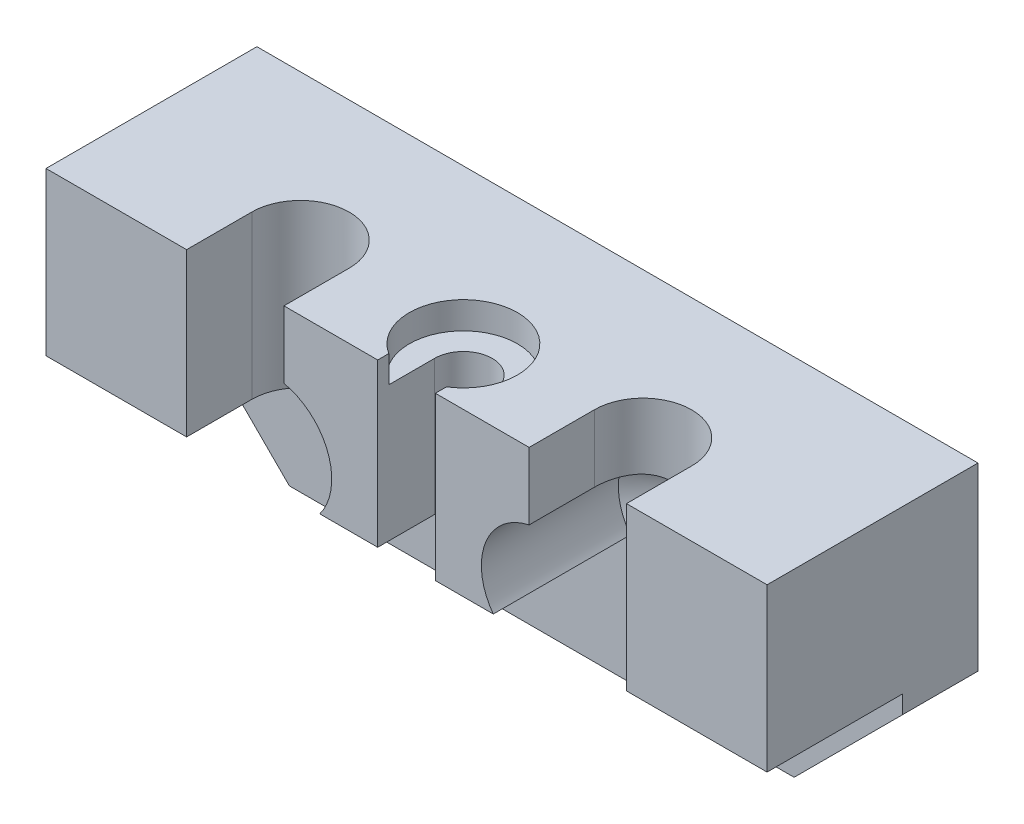
SolidWorks part; units mm, degrees
ref_plane "Front Plane" through (0, 0, 0) normal (0, 0, 1) x (1, 0, 0)
ref_plane "Top Plane" through (0, 0, 0) normal (0, 1, 0) x (1, 0, 0)
ref_plane "Right Plane" through (0, 0, 0) normal (1, 0, 0) x (0, 0, -1)
sketch "Sketch1" plane through (0, 0, 0) normal (0, 0, 1) x (1, 0, 0)
  line L1 (-20, 0) -> (20, 0)
  line L2 (-20, 0) -> (-20, 16)
  line L3 (-20, 16) -> (20, 16)
  line L4 (20, 0) -> (20, 16)
  dimension "D2" = 40
  dimension "D3" = 16
extrude "Boss-Extrude1" add sketch "Sketch1" along normal blind 12
sketch "Sketch2" plane through (0, 0, 12) normal (0, 0, 1) x (1, 0, 0)
  line L0 (0, 8) -> (0, 9) construction
  line L2 (-7.5, 9) -> (7.5, 9) construction
  line L3 (20, 16) -> (-20, 16) construction
  line L4 (-7.5, 5) -> (-7.5, 13) construction
  line L5 (-9.15, 5) -> (-9.15, 13) construction
  line L6 (-5.85, 5) -> (-5.85, 13) construction
  line L7 (7.5, 5) -> (7.5, 13) construction
  line L8 (5.85, 5) -> (5.85, 13) construction
  line L9 (9.15, 5) -> (9.15, 13) construction
  line L10 (-16, 8) -> (16, 8) construction
  arc A0 (-9.15, 5) -> (-5.85, 5) centre (-7.5, 5) ccw construction
  arc A1 (-5.85, 13) -> (-9.15, 13) centre (-7.5, 13) ccw construction
  arc A2 (5.85, 5) -> (9.15, 5) centre (7.5, 5) ccw construction
  arc A3 (9.15, 13) -> (5.85, 13) centre (7.5, 13) ccw construction
  circle A4 centre (-16, 8) radius 1.7784 construction
  circle A5 centre (16, 8) radius 1.7784 construction
  circle A6 centre (-7.5, 9) radius 1.65
  circle A7 centre (7.5, 9) radius 1.65
  point P8 (-7.5, 9)
  point P15 (7.5, 9)
  dimension "D1" = 1.65
  dimension "D2" = 8
  dimension "D3" = 7
  dimension "D4" = 15
  dimension "D5" = 1
  dimension "D6" = 32
extrude "Cut-Extrude1" cut sketch "Sketch2" against normal through all
sketch "Sketch5" plane through (0, 16, 0) normal (0, 1, 0) x (1, 0, 0)
  line L0 (-12.2, -8.3849) -> (-12.2, -12)
  line L1 (20, -12) -> (-20, -12) construction
  line L3 (-12.2, -12) -> (-6.8, -12)
  line L4 (-6.8, -12) -> (-6.8, -8.3849)
  arc A0 (-6.8, -8.3849) -> (-12.2, -8.3849) centre (-9.5, -8.3849) ccw
  dimension "D2" = 5.4
extrude "Cut-Extrude4" cut sketch "Sketch5" against normal through all
sketch "Sketch6" plane through (20, 0, 0) normal (1, 0, 0) x (0, 0, -1)
  line L0 (-12, 7) -> (-4.5, 7)
  line L3 (-4.5, 7) -> (-4.5, 0)
  line L4 (-12, 0) -> (0, 0) construction
  line L5 (-4.5, 0) -> (-12, 0)
  line L6 (-12, 0) -> (-12, 7)
  line L8 (-12, 16) -> (0, 16) construction
  line L9 (0, 0) -> (0, 16) construction
  dimension "D1" = 9
  dimension "D2" = 4.5
extrude "Cut-Extrude5" cut sketch "Sketch6" against normal through all
sketch "Sketch8" plane through (0, 16, 0) normal (0, 1, 0) x (1, 0, 0)
  line L0 (-1.6, -8.8461) -> (-1.6, -12)
  line L2 (20, -12) -> (-6.8, -12) construction
  line L3 (-1.6, -12) -> (1.6, -12)
  line L4 (1.6, -12) -> (1.6, -8.8461)
  arc A0 (1.6, -9.0461) -> (-1.6, -9.0461) centre (0, -9.0461) ccw construction
  arc A1 (1.6, -8.8461) -> (-1.6, -8.8461) centre (0, -8.8461) ccw
  dimension "D1" = 1.6
  dimension "D2" = 0.2
extrude "Cut-Extrude7" cut sketch "Sketch8" against normal through all
sketch "Sketch9" plane through (0, 0, 12) normal (0, 0, 1) x (1, 0, 0)
  circle A0 centre (-7.5, 9) radius 3.35
  circle A1 centre (7.5, 9) radius 3.35
  dimension "D1" = 6.7
extrude "Cut-Extrude8" cut sketch "Sketch9" against normal up to surface (7.5 mm away) up to face at (0, 3.5, 4.5)
chamfer "Chamfer5" distance 1.8 angle 45 2 edges at (-7.5, 10.65, 4.5) (7.5, 10.65, 4.5)
chamfer "Chamfer6" distance 6 angle 45 2 edges at (20, 0, 2.25) (-20, 0, 2.25)
chamfer "Chamfer7" distance 0.3 angle 45 8 edges at (0, 16, 0) (-20, 11, 0) (-17, 3, 0) (0, 0, 0) (17, 3, 0) (20, 11, 0) (-5.85, 9, 0) (9.15, 9, 0)
sketch "Sketch11" plane through (0, 16, 0) normal (0, 1, 0) x (1, 0, 0)
  circle A0 centre (0, -8.8461) radius 3
  arc A1 (1.6, -8.8461) -> (-1.6, -8.8461) centre (0, -8.8461) ccw construction
  dimension "D1" = 6
extrude "Cut-Extrude9" cut sketch "Sketch11" against normal blind 1.5 contours A0
ref_plane "Plane1" through (0, 0, 0) normal (-1, 0, 0) x (0, 0, 1)
mirror "Mirror1" about plane through (0, 0, 0) normal (-1, 0, 0) of "Cut-Extrude4"
equation "\"y-cross-rib-thickness\"=6"
equation "\"y-rib-thickness\"=6"
equation "\"bed-plate-thickness\"=6"
equation "\"x-plate-thickness\"=5"
equation "\"rod-diameter\"=12"
equation "\"t-nut-hole-diameter\"=3"
equation "\"y-plate-thickness\"=5"
equation "\"enclosure-thickness\"=0.6"
equation "\"M3-Clearance\"=3.3"
equation "\"M4-Clearance\"=4.3"
equation "\"M5-Clearance\"=5.3"
equation "\"M6-Clearance\"=6.3"
equation "\"M8-Clearance\"=8.3"
equation "\"623-Bearing-Dia\"=11.2"
